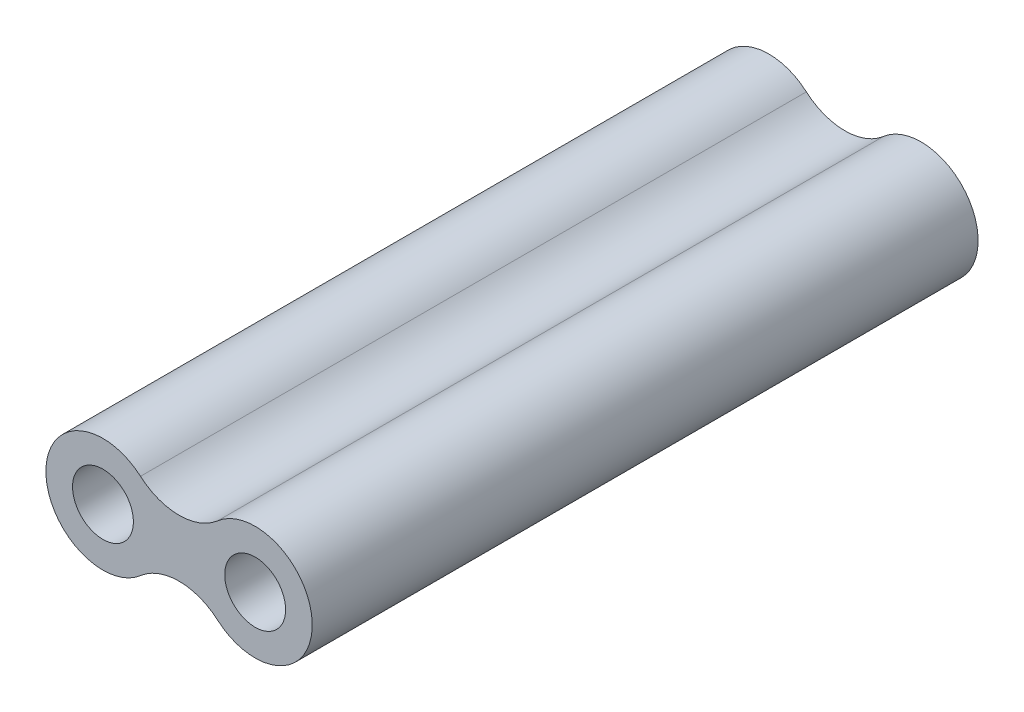
SolidWorks part; units mm, degrees
material "Rubber"
ref_plane "Front Plane" through (0, 0, 0) normal (0, 0, 1) x (1, 0, 0)
ref_plane "Top Plane" through (0, 0, 0) normal (0, 1, 0) x (1, 0, 0)
ref_plane "Right Plane" through (0, 0, 0) normal (1, 0, 0) x (0, 0, -1)
ref_axis "X" through (-88.99, 0, 0) along (1, 0, 0)
ref_axis "Y" through (0, 55, 0) along (0, -1, 0)
ref_axis "Z" through (0, 0, -88.99) along (0, 0, 1)
sketch "Sketch1" plane through (0, 0, 0) normal (0, 0, 1) x (1, 0, 0)
  circle A0 centre (0, 0) radius 1.5 construction
  circle A1 centre (0, 0) radius 3
  dimension "D1" = 3
  dimension "D2" = 6
extrude "Boss-Extrude1" add sketch "Sketch1" along normal mid plane 35
sketch "Sketch5" plane through (0, 0, 17.5) normal (0, 0, 1) x (1, 0, 0)
  point P0 (0, 0)
hole_wizard "M3 Clearance Hole" positions "Sketch5" profile "Sketch4" hole size "M3" standard "ANSI Metric" end condition through all
sketch "Sketch4" plane through (0, 0, 17.5) normal (1, 0, 0) x (0, -1, 0)
  line L0 (0, 0) -> (0, 35)
  line L1 (0, 35) -> (1.6, 35)
  line L2 (1.6, 35) -> (1.6, 0)
  line L5 (1.6, 0) -> (0, 0)
  line L11 (0, -6.35) -> (0, 107.95) construction
  dimension "Thru Hole Dia." = 3.2
  dimension "Thru Hole Depth" = 35
sketch "Sketch2" plane through (0, 0, 0) normal (0, 0, 1) x (1, 0, 0)
  line L0 (0, 0) -> (8, 0) construction
  line L1 (4, 1.5) -> (4, -1.5) construction
  circle A0 centre (8, 0) radius 1.5 construction
  circle A1 centre (8, 0) radius 3
  circle A3 centre (0, 0) radius 3 construction
  circle A4 centre (0, 0) radius 1.5 construction
  arc A5 (1.9726, 2.2603) -> (6.0274, 2.2603) centre (4, 4.5833) ccw
  arc A6 (1.9726, -2.2603) -> (6.0274, -2.2603) centre (4, -4.5833) cw
  circle A7 centre (0, 0) radius 3
  dimension "D1" = 3
  dimension "D2" = 8
extrude "Boss-Extrude2" add sketch "Sketch2" along normal up to surface and the other way up to surface contours A1 | A7 A6 A1 A5 region at (8, 0, 0) region at (4, 0, 0) up to face at (1.6, 0, 17.5) other way up to face at (1.6, 0, -17.5)
sketch "Sketch8" plane through (0, 0, 17.5) normal (0, 0, 1) x (1, 0, 0)
  point P0 (8, 0)
hole_wizard "M3 Clearance Hole2" positions "Sketch8" profile "Sketch7" hole size "M3" standard "ANSI Metric" end condition through all
sketch "Sketch7" plane through (8, 0, 17.5) normal (1, 0, 0) x (0, -1, 0)
  line L0 (0, 0) -> (0, 35)
  line L1 (0, 35) -> (1.6, 35)
  line L2 (1.6, 35) -> (1.6, 0)
  line L5 (1.6, 0) -> (0, 0)
  line L11 (0, -6.35) -> (0, 107.95) construction
  dimension "Thru Hole Dia." = 3.2
  dimension "Thru Hole Depth" = 35
equation "\"Spacing\"= 8mm"
equation "\"D2@Sketch2\"=\"Spacing\""
